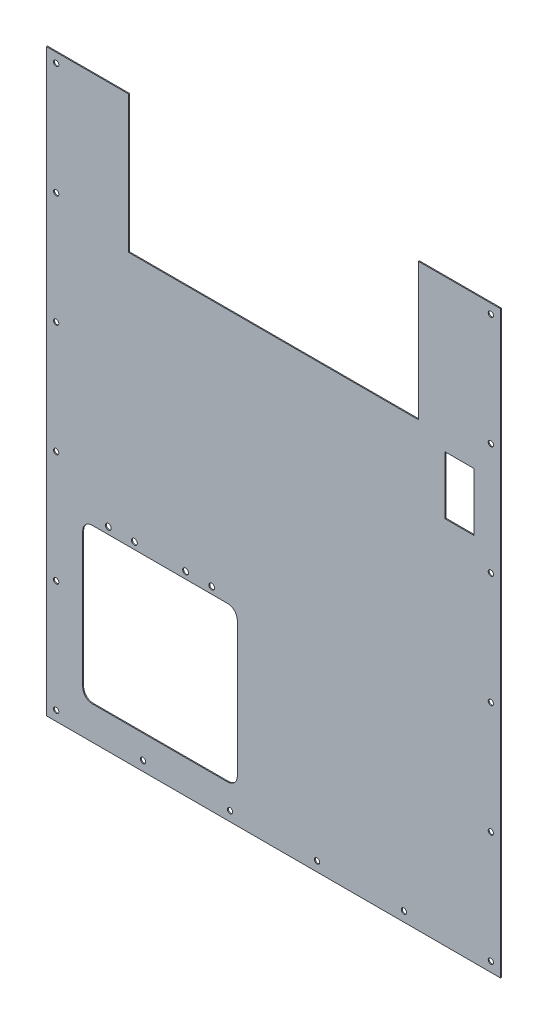
SolidWorks part; units mm, degrees
ref_plane "정면" through (0, 0, 0) normal (0, 0, 1) x (1, 0, 0)
ref_plane "윗면" through (0, 0, 0) normal (0, 1, 0) x (1, 0, 0)
ref_plane "우측면" through (0, 0, 0) normal (1, 0, 0) x (0, 0, -1)
sketch "스케치1" plane through (0, 0, 0) normal (0, 0, 1) x (1, 0, 0)
  line L1 (-235, -300) -> (235, -300)
  line L2 (-235, -300) -> (-235, 300)
  line L3 (-235, 300) -> (235, 300)
  line L4 (235, -300) -> (235, 300)
  line L5 (-235, -300) -> (235, 300) construction
  line L6 (-235, 300) -> (235, -300) construction
  line L7 (-225, -290) -> (225, -290) construction
  line L8 (-225, -290) -> (-225, 290) construction
  line L9 (-225, 290) -> (225, 290) construction
  line L10 (225, -290) -> (225, 290) construction
  line L11 (-225, -290) -> (225, 290) construction
  line L12 (-225, 290) -> (225, -290) construction
  line L13 (-150, 300) -> (150, 300)
  line L14 (-150, 300) -> (-150, 158)
  line L15 (-150, 158) -> (150, 158)
  line L16 (150, 300) -> (150, 158)
  line L17 (-150, 300) -> (150, 158) construction
  line L18 (-150, 158) -> (150, 300) construction
  point P0 (0, 0)
  point P6 (0, 0)
  point P11 (-45, -290)
  point P12 (-225, 290)
  point P13 (225, 290)
  point P14 (225, -290)
  point P15 (-225, -290)
  point P17 (45, -290)
  point P18 (-135, -290)
  point P19 (135, -290)
  point P20 (-225, 58)
  point P21 (-45, 290)
  point P23 (45, 290)
  point P24 (-135, 290)
  point P25 (135, 290)
  point P28 (-225, -58)
  point P29 (-225, 174)
  point P30 (-225, -174)
  point P32 (225, 58)
  point P34 (225, -58)
  point P35 (225, 174)
  point P36 (225, -174)
  point P40 (0, 229)
  point P41 (0, 0)
  point P42 (0, 0)
  point P43 (0, 0)
  point P44 (0, 0)
  point P45 (31.5364, -300)
  point P46 (0, 0)
  point P47 (0, 0)
  point P48 (0, 0)
  point P49 (0, 0)
  dimension "D1" = 470
  dimension "D2" = 600
  dimension "D3" = 10
  dimension "D4" = 10
  dimension "D5" = 90
  dimension "D6" = 90
  dimension "D7" = 90
  dimension "D8" = 90
  dimension "D9" = 116
  dimension "a" = 116
  dimension "D10" = 116
  dimension "D11" = 116
  dimension "D12" = 300
  dimension "D13" = 142
extrude "보스-돌출1" add sketch "스케치1" along normal blind 1 contours L3 L4 L1 L2
hole_wizard "M5 여유 구멍1" positions "스케치2" profile "스케치3" hole size "M5" standard "KS" end condition through all
sketch "스케치2" plane through (0, 0, 0) normal (0, 0, -1) x (-1, 0, 0)
  point P0 (-225, 290)
  point P3 (-135, 290)
  point P6 (-45, 290)
  point P12 (45, 290)
  point P15 (135, 290)
  point P18 (225, 290)
  point P21 (225, 174)
  point P24 (225, 58)
  point P30 (225, -58)
  point P33 (225, -174)
  point P36 (225, -290)
  point P39 (-225, 174)
  point P42 (-225, 58)
  point P48 (-225, -58)
  point P51 (-225, -174)
  point P54 (-225, -290)
  point P57 (-135, -290)
  point P60 (-45, -290)
  point P66 (45, -290)
  point P69 (135, -290)
sketch "스케치3" plane through (225, 290, 0) normal (1, 0, 0) x (0, 1, 0)
  line L0 (0, 0) -> (0, 1)
  line L1 (0, 1) -> (2.75, 1)
  line L2 (2.75, 1) -> (2.75, 0)
  line L5 (2.75, 0) -> (0, 0)
  line L11 (0, -6.35) -> (0, 107.95) construction
  dimension "관통 구멍 지름" = 5.5
  dimension "관통 구멍 깊이" = 1
extrude "컷-돌출3" cut sketch "스케치1<3>" along normal blind 10 contours L14 L15 L16 L13
sketch "스케치1<3>" plane through (0, 0, 0) normal (0, 0, 1) x (1, 0, 0) same geometry as "스케치1"
sketch "스케치4" plane through (0, 0, 1) normal (0, 0, 1) x (1, 0, 0)
  line L0 (-150, 158) -> (150, 158) construction
  line L1 (177.5, 143) -> (207.5, 143)
  line L2 (177.5, 143) -> (177.5, 83)
  line L3 (177.5, 83) -> (207.5, 83)
  line L4 (207.5, 143) -> (207.5, 83)
  line L5 (177.5, 143) -> (207.5, 83) construction
  line L6 (177.5, 83) -> (207.5, 143) construction
  line L7 (-187.5, -105.5) -> (-47.5, -105.5)
  line L8 (-197.5, -115.5) -> (-197.5, -255.5)
  line L9 (-187.5, -265.5) -> (-47.5, -265.5)
  line L10 (-37.5, -115.5) -> (-37.5, -255.5)
  line L11 (-197.5, -105.5) -> (-37.5, -265.5) construction
  line L12 (-197.5, -265.5) -> (-37.5, -105.5) construction
  line L13 (150, 193) -> (235, 193) construction
  line L14 (150, 300) -> (150, 158) construction
  line L17 (235, -300) -> (235, 300) construction
  line L18 (0, 158) -> (0, -300) construction
  line L19 (-235, -300) -> (235, -300) construction
  line L20 (-235, -71) -> (235, -71) construction
  line L21 (-235, -300) -> (-235, 300) construction
  line L22 (0, -185.5) -> (-235, -185.5) construction
  line L23 (-117.5, -71) -> (-117.5, -300) construction
  arc A0 (-47.5, -105.5) -> (-37.5, -115.5) centre (-47.5, -115.5) cw
  arc A1 (-37.5, -255.5) -> (-47.5, -265.5) centre (-47.5, -255.5) cw
  arc A2 (-197.5, -255.5) -> (-187.5, -265.5) centre (-187.5, -255.5) ccw
  arc A3 (-197.5, -115.5) -> (-187.5, -105.5) centre (-187.5, -115.5) cw
  point P4 (192.5, 113)
  point P9 (-117.5, -185.5)
  point P14 (192.5, 193)
  point P23 (-117.5, -185.5)
  point P27 (0, -71)
  point P34 (-117.5, -185.5)
  dimension "D6" = 10
  dimension "D1" = 60
  dimension "D2" = 30
  dimension "D3" = 15
  dimension "D4" = 160
  dimension "D5" = 160
  dimension "D7" = 50
extrude "컷-돌출4" cut sketch "스케치4" against normal blind 10
sketch "스케치5" plane through (0, 0, 1) normal (0, 0, 1) x (1, 0, 0)
  line L0 (-47.5, -105.5) -> (-187.5, -105.5) construction
  line L1 (-177, -91.5) -> (-138, -91.5)
  line L2 (-177, -91.5) -> (-177, -105.5)
  line L3 (-177, -105.5) -> (-138, -105.5)
  line L4 (-138, -91.5) -> (-138, -105.5)
  line L5 (-177, -91.5) -> (-138, -105.5) construction
  line L6 (-177, -105.5) -> (-138, -91.5) construction
  line L7 (-197.5, -119.5) -> (-37.5, -119.5) construction
  line L8 (-197.5, -115.5) -> (-197.5, -255.5) construction
  line L9 (-37.5, -255.5) -> (-37.5, -115.5) construction
  line L10 (-117.5, -119.5) -> (-117.5, -105.5) construction
  line L11 (-117.5, -117.5) -> (-197.5, -117.5) construction
  line L12 (-58, -105.5) -> (-97, -91.5) construction
  line L13 (-58, -91.5) -> (-97, -105.5) construction
  line L14 (-97, -91.5) -> (-97, -105.5)
  line L15 (-58, -105.5) -> (-97, -105.5)
  line L16 (-58, -91.5) -> (-58, -105.5)
  line L17 (-58, -91.5) -> (-97, -91.5)
  circle A0 centre (-171, -98.5) radius 3
  circle A1 centre (-144, -98.5) radius 3
  circle A4 centre (-91, -98.5) radius 3
  circle A5 centre (-64, -98.5) radius 3
  point P12 (-157.5, -98.5)
  point P23 (-157.5, -117.5)
  point P32 (-77.5, -98.5)
  dimension "D3" = 6
  dimension "D4" = 6
  dimension "D1" = 39
  dimension "D2" = 14
  dimension "D5" = 6
  dimension "D6" = 6
  dimension "D7" = 2
  dimension "D8" = 12
extrude "컷-돌출5" cut sketch "스케치5" against normal blind 10 contours A0 | A1 | A4 | A5
